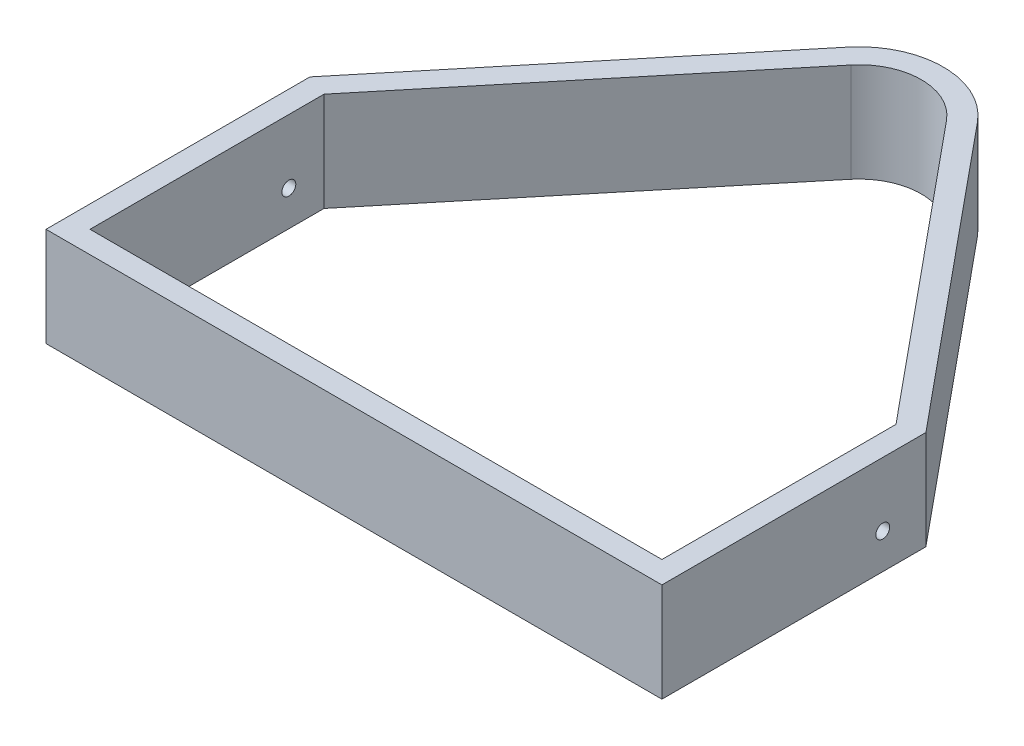
SolidWorks part; units mm, degrees
ref_plane "Front Plane" through (0, 0, 0) normal (0, 0, 1) x (1, 0, 0)
ref_plane "Top Plane" through (0, 0, 0) normal (0, 1, 0) x (1, 0, 0)
ref_plane "Right Plane" through (0, 0, 0) normal (1, 0, 0) x (0, 0, -1)
sketch "Sketch1" plane through (0, 0, 0) normal (0, 1, 0) x (1, 0, 0)
  line L0 (-88.9, 0) -> (88.9, 0)
  line L1 (-88.9, 38.1) -> (88.9, 38.1) construction
  line L2 (-88.9, 0) -> (-88.9, 76.2)
  line L3 (-88.9, 38.1) -> (0, 145.8631) construction
  line L8 (0, 145.8631) -> (88.9, 38.1) construction
  line L13 (88.9, 0) -> (88.9, 76.2)
  line L14 (-88.9, 76.2) -> (-18.7027, 161.292)
  line L15 (18.7027, 161.292) -> (88.9, 76.2)
  line L16 (-82.55, 6.35) -> (-82.55, 73.9188)
  line L17 (-82.55, 73.9188) -> (-13.8044, 157.2511)
  line L18 (13.8044, 157.2511) -> (82.55, 73.9188)
  line L19 (82.55, 6.35) -> (82.55, 73.9188)
  line L20 (-82.55, 6.35) -> (82.55, 6.35)
  arc A0 (-18.7027, 161.292) -> (18.7027, 161.292) centre (0, 145.8631) cw
  arc A2 (-13.8044, 157.2511) -> (13.8044, 157.2511) centre (0, 145.8631) cw
  point P4 (0, 0)
  dimension "D1" = 177.8
  dimension "D2" = 139.7
  dimension "D3" = 38.1
  dimension "D4" = 76.2
  dimension "D6" = 6.35
extrude "Boss-Extrude1" add sketch "Sketch1" along normal blind 28.575
sketch "Sketch2" plane through (0, 0, 0) normal (1, 0, 0) x (0, 0, -1)
  line L1 (0, 0) -> (76.2, 0) construction
  line L4 (73.9188, 28.575) -> (73.9188, 0) construction
  circle A0 centre (63.7588, 10.16) radius 10.16 construction
  circle A1 centre (63.7588, 10.16) radius 2
  dimension "D1" = 20.32
  dimension "D2" = 4
extrude "Cut-Extrude1" cut sketch "Sketch2" against normal up to next from surface starting at face at (-82.55, 14.2875, -40.1344)
extrude "Cut-Extrude3" cut sketch "Sketch2<2>" along normal up to next from surface starting at face at (82.55, 14.2875, -40.1344)
sketch "Sketch2<2>" plane through (0, 0, 0) normal (1, 0, 0) x (0, 0, -1) same geometry as "Sketch2"
